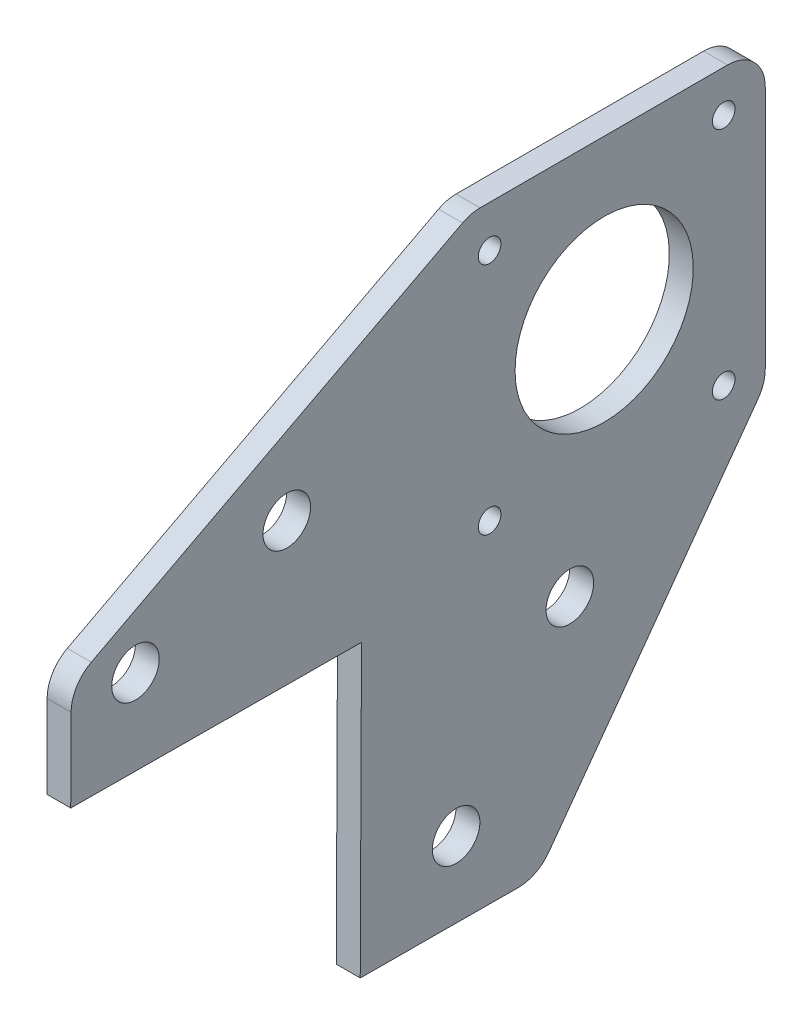
SolidWorks part; units mm, degrees
ref_plane "Front Plane" through (0, 0, 0) normal (0, 0, 1) x (1, 0, 0)
ref_plane "Top Plane" through (0, 0, 0) normal (0, 1, 0) x (1, 0, 0)
ref_plane "Right Plane" through (0, 0, 0) normal (1, 0, 0) x (0, 0, -1)
sketch "Sketch1" plane through (0, 0, 0) normal (1, 0, 0) x (0, 0, -1)
  line L0 (15.8652, 80.395) -> (48.6265, 80.395)
  line L1 (53.6265, 75.395) -> (53.6265, 43.0231)
  line L2 (0.0001, 0.0159) -> (0.1676, 38.4279)
  line L3 (0.1676, 38.4279) -> (-38.3318, 38.6675)
  line L4 (-38.3318, 38.6675) -> (-38.284, 49.629)
  line L5 (-35.6071, 54.0347) -> (13.5421, 79.8225)
  line L6 (0.0001, 0.0159) -> (20.906, -0.0821)
  line L7 (24.9739, 1.9781) -> (52.671, 40.0834)
  arc A0 (53.6265, 75.395) -> (48.6265, 80.395) centre (48.6265, 75.395) ccw
  arc A1 (15.8652, 80.395) -> (13.5421, 79.8225) centre (15.8652, 75.395) ccw
  arc A2 (-38.284, 49.629) -> (-35.6071, 54.0347) centre (-33.284, 49.6072) cw
  arc A3 (53.6265, 43.0231) -> (52.671, 40.0834) centre (48.6265, 43.0231) cw
  arc A4 (20.906, -0.0821) -> (24.9739, 1.9781) centre (20.9294, 4.9178) ccw
  circle A5 centre (17.1303, 43.8912) radius 1.5
  ellipse E0 centre (48.1292, 43.8943) end of major axis (47.3949, 45.2023) minor radius 1.5
  ellipse E1 centre (17.1266, 74.8912) end of major axis (16.3923, 76.1992) minor radius 1.5
  ellipse E2 centre (48.1266, 74.8949) end of major axis (47.3923, 76.2029) minor radius 1.5
  spline S0 degree 3 poles (27.6693, 48.2059) (32.3027, 47.2849) (36.9358, 48.207) (40.8633, 50.832) (43.4874, 54.7602) (44.4084, 59.3935) (43.4863, 64.0266) (40.8613, 67.9542) (36.9331, 70.5782) (32.2998, 71.4993) (27.6667, 70.5771) (23.7391, 67.9521) (21.1151, 64.024) (20.194, 59.3906) (21.1162, 54.7575) (23.7411, 50.83) (27.6693, 48.2059) (32.3027, 47.2849) (36.9358, 48.207) knots -1.178097 -0.785398 -0.392699 0 0.392699 0.785398 1.178097 1.570796 1.963495 2.356194 2.748894 3.141593 3.534292 3.926991 4.31969 4.712389 5.105088 5.497787 5.890486 6.283185 6.675884 7.068583 7.461283 only from (32.3026, 47.5921) to (32.3026, 47.5921)
  dimension "D1" = 5
base flange "Base-Flange1" sketch "Sketch1" thickness 3.175 reverse thickness direction no parameters "D1"=3.175
extrude "Cut-Extrude1" cut sketch "Sketch2" against normal blind 10
sketch "Sketch2" plane through (-3.175, -854.2446, -1311.5874) normal (-1, 0, 0) x (0, 0, 1)
  circle A4 centre (1283.8331, 884.1307) radius 3.15
  circle A5 centre (1298.893, 864.2011) radius 3.15
  circle A6 centre (1341.3438, 904.1579) radius 3.15
  circle A7 centre (1321.3114, 911.5706) radius 3.15
sketch "Bend-Lines1" [suppressed] plane through (0, 0, 0) normal (0, 1, 0) x (1, 0, 0)
sketch "Bounding-Box1" [suppressed] plane through (0, 0, 0) normal (0, 1, 0) x (1, 0, 0)
sheet metal parameters "Sheet-Metal1" thickness 3.175 parameters "D1"=3.175
flat pattern "Flat-Pattern1" [suppressed]
sketch "Bend-Lines2" plane through (0, 0, 0) normal (0, 1, 0) x (1, 0, 0)
sketch3d "Bounding-Box2" [suppressed]
  line L0 (-86.7861, 31.1666, 0) -> (5.182, 30.7655, 0) construction
  line L1 (-87.1371, -49.3189, 0) -> (4.831, -49.72, 0) construction
  line L2 (-86.7861, 31.1666, 0) -> (-87.1371, -49.3189, 0) construction
  line L3 (5.182, 30.7655, 0) -> (4.831, -49.72, 0) construction
sheet metal parameters "Sheet-Metal2" thickness 3.175 parameters "D1"=3.175
flat pattern "Flat-Pattern1"
sketch "Bend-Lines2" plane through (0, 0, 0) normal (0, 1, 0) x (1, 0, 0)
sketch3d "Bounding-Box2" [suppressed]
  line L0 (54.2183, 60.8117, 0) -> (-11.5353, -4.398, 0) construction
  line L1 (110.4853, 4.0753, 0) -> (44.7317, -61.1344, 0) construction
  line L2 (54.2183, 60.8117, 0) -> (110.4853, 4.0753, 0) construction
  line L3 (-11.5353, -4.398, 0) -> (44.7317, -61.1344, 0) construction
